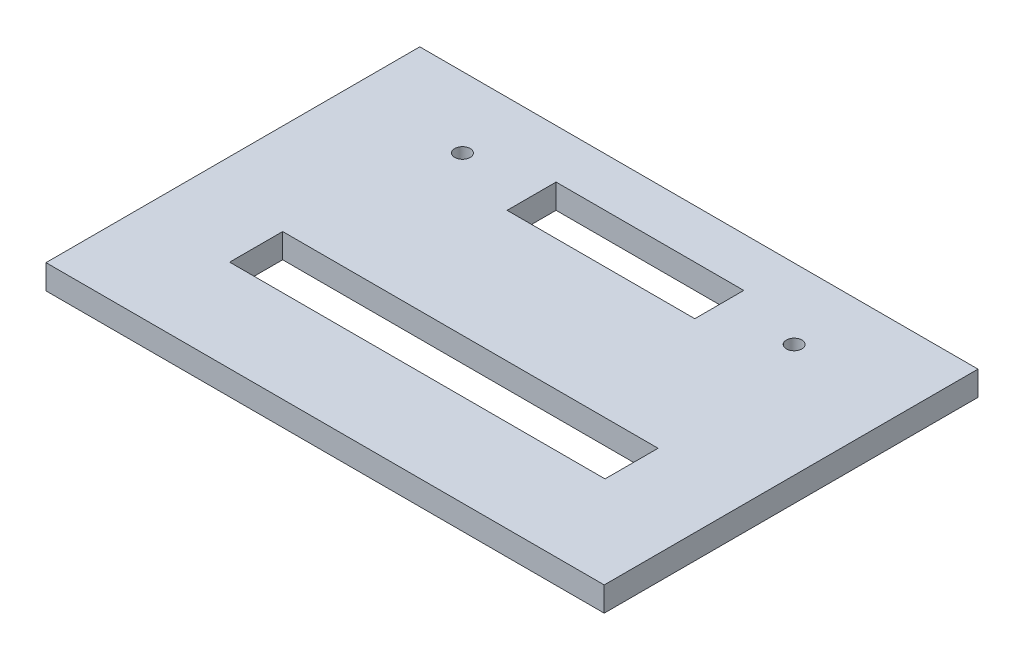
SolidWorks part; units mm, degrees
material "ABS"
ref_plane "Front Plane" through (0, 0, 0) normal (0, 0, 1) x (1, 0, 0)
ref_plane "Top Plane" through (0, 0, 0) normal (0, 1, 0) x (1, 0, 0)
ref_plane "Right Plane" through (0, 0, 0) normal (1, 0, 0) x (0, 0, -1)
sketch "Sketch1" plane through (0, 0, 0) normal (0, 1, 0) x (1, 0, 0)
  line L1 (-34.2, -22.9) -> (34.2, -22.9)
  line L2 (-34.2, -22.9) -> (-34.2, 22.9)
  line L3 (-34.2, 22.9) -> (34.2, 22.9)
  line L4 (34.2, -22.9) -> (34.2, 22.9)
  line L5 (-34.2, -22.9) -> (34.2, 22.9) construction
  line L6 (-34.2, 22.9) -> (34.2, -22.9) construction
  point P0 (0, 0)
  dimension "D1" = 45.8
  dimension "D2" = 68.4
extrude "Boss-Extrude1" add sketch "Sketch1" along normal blind 3
sketch "Sketch2" plane through (0, 3, 0) normal (0, 1, 0) x (1, 0, 0)
  line L0 (34.2, 22.9) -> (-34.2, 22.9) construction
  line L1 (0, 0) -> (0, 22.9) construction
  circle A0 centre (-20.32, 14.25) radius 0.95
  circle A1 centre (20.32, 14.25) radius 0.95
  dimension "D1" = 1.9
  dimension "D2" = 8.65
  dimension "D3" = 20.32
extrude "Cut-Extrude1" cut sketch "Sketch2" against normal through all
sketch "Sketch3" plane through (0, 3, 0) normal (0, 1, 0) x (1, 0, 0)
  line L0 (34.2, 22.9) -> (-34.2, 22.9) construction
  line L1 (11.5, 16.9) -> (-11.5, 16.9)
  line L2 (11.5, 16.9) -> (11.5, 10.9)
  line L3 (11.5, 10.9) -> (-11.5, 10.9)
  line L4 (-11.5, 16.9) -> (-11.5, 10.9)
  line L6 (23, -5.1) -> (-23, -5.1)
  line L7 (23, -5.1) -> (23, -11.6)
  line L8 (23, -11.6) -> (-23, -11.6)
  line L9 (-23, -5.1) -> (-23, -11.6)
  point P10 (0, 10.9)
  point P12 (0, -5.1)
  dimension "D1" = 6
  dimension "D2" = 6
  dimension "D3" = 22
  dimension "D4" = 28.5
  dimension "D5" = 46
  dimension "D6" = 23
extrude "Cut-Extrude2" cut sketch "Sketch3" against normal through all
equation "\"smallPulleyTeeth\"= 30"
equation "\"largePulleyTeeth\"= 30"
equation "\"eighthThick\"= 3.0mm"
equation "\"sixteenthThick\" = 1.7mm"
equation "\"quarterThick\"=6.0mm"
equation "\"OD\" = 145mm"
equation "\"puckAngle\" = 60.5deg"
equation "\"puckDiam\" = 76.5mm"
equation "\"puckDist\" = 85mm"
equation "\"scoopFillet\" = 5mm"
equation "\"axlePress\" = 5.9mm"
equation "\"press\" = 0.2mm"
equation "\"wheelClear\" = 0.3mm"
equation "\"10-32clear\" = 4.8mm"
equation "\"10-32tap\" = 4.45mm"
equation "\"6-32clear\" = 3.3mm"
equation "\"8-32clear\" = 4.0mm"
equation "\"4-40clear\" = 3.0mm"
equation "\"wheelHeight\" = 22mm"
equation "\"wheelWell\" = 65mm"
equation "\"ledSmall\" = 3.1mm"
equation "\"ledLarge\" = 4.2mm"
equation "\"ledLength\" = 4.2mm"
equation "\"4-40close\" = 2.7mm"
equation "\"4-40nutThick\" = 2.2mm"
equation "\"4-40nutWidth\" = 6.2mm"
equation "\"4-40insertHeight\" = 3.5mm"
equation "\"4-40insert\" = 4.25mm"
equation "\"D1@Boss-Extrude1\"=\"eighthThick\""
